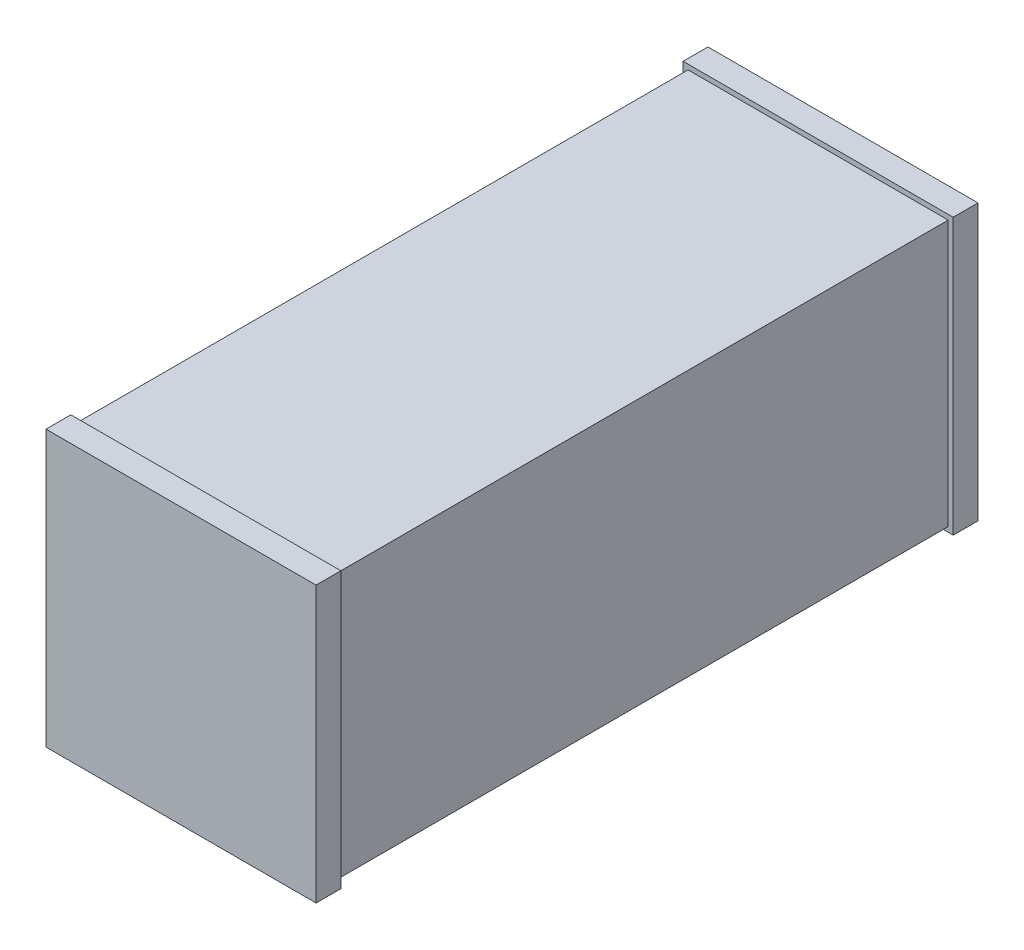
SolidWorks part; units mm, degrees
ref_plane "Front Plane" through (0, 0, 0) normal (0, 0, 1) x (1, 0, 0)
ref_plane "Top Plane" through (0, 0, 0) normal (0, 1, 0) x (1, 0, 0)
ref_plane "Right Plane" through (0, 0, 0) normal (1, 0, 0) x (0, 0, -1)
sketch "Sketch1" plane through (0, 0, 0) normal (0, 0, 1) x (1, 0, 0)
  line L1 (0, 0) -> (103.632, 0)
  line L2 (0, 0) -> (0, -105.664)
  line L3 (0, -105.664) -> (103.632, -105.664)
  line L4 (103.632, 0) -> (103.632, -105.664)
  dimension "D1" = 103.632
  dimension "D2" = 105.664
extrude "Boss-Extrude1" add sketch "Sketch1" against normal blind 9.525
sketch "Sketch2" plane through (0, 0, -9.525) normal (0, 0, -1) x (-1, 0, 0)
  line L0 (-103.632, 0) -> (0, 0) construction
  line L1 (-101.727, -1.905) -> (-1.905, -1.905)
  line L2 (-101.727, -1.905) -> (-101.727, -103.759)
  line L3 (-101.727, -103.759) -> (-1.905, -103.759)
  line L4 (-1.905, -1.905) -> (-1.905, -103.759)
  line L5 (-103.632, -105.664) -> (-103.632, 0) construction
  line L6 (0, 0) -> (0, -105.664) construction
  line L7 (0, -105.664) -> (-103.632, -105.664) construction
  dimension "D1" = 1.905
  dimension "D2" = 1.905
  dimension "D3" = 1.905
  dimension "D4" = 1.905
extrude "Boss-Extrude2" add sketch "Sketch2" along normal blind 234.95
sketch "Sketch4" plane through (0, 0, -244.475) normal (0, 0, -1) x (-1, 0, 0)
  line L8 (0, 0) -> (-103.632, 0)
  line L9 (-103.632, 0) -> (-103.632, -105.664)
  line L10 (-103.632, -105.664) -> (0, -105.664)
  line L11 (0, -105.664) -> (0, 0)
  line L12 (0, 0) -> (-103.632, 0)
  line L13 (-103.632, 0) -> (-103.632, -105.664)
  line L14 (-103.632, -105.664) -> (0, -105.664)
  line L15 (0, -105.664) -> (0, 0)
  dimension "D1" = 0
extrude "Boss-Extrude5" add sketch "Sketch4" along normal blind 9.525
sketch "Sketch5" plane through (0, -103.759, 0) normal (0, -1, 0) x (1, 0, 0)
  line L0 (101.727, -9.525) -> (1.905, -9.525) construction
  line L2 (15.621, -19.05) -> (1.905, -19.05) construction
  line L3 (1.905, -244.475) -> (1.905, -9.525) construction
  line L4 (88.011, -19.05) -> (101.727, -19.05) construction
  line L5 (101.727, -244.475) -> (101.727, -9.525) construction
  line L6 (15.621, -234.95) -> (1.905, -234.95) construction
  line L7 (88.011, -234.95) -> (101.727, -234.95) construction
  point P0 (15.621, -19.05)
  point P1 (88.011, -19.05)
  point P2 (15.621, -234.95)
  point P3 (88.011, -234.95)
  dimension "D1" = 72.39
  dimension "D2" = 215.9
  dimension "D3" = 9.525
hole_wizard "Tap Drill for #6-32 Tap1" positions "Sketch6" profile "Sketch7" hole size "#6-32" standard "ANSI Inch"
sketch "Sketch6" plane through (0, -103.759, 0) normal (0, -1, 0) x (-1, 0, 0)
  point P0 (-88.011, 234.95)
  point P3 (-15.621, 234.95)
  point P6 (-88.011, 19.05)
  point P9 (-15.621, 19.05)
sketch "Sketch7" plane through (88.011, -103.759, -234.95) normal (1, 0, 0) x (0, 0, -1)
  line L0 (0, 0) -> (0, 4.7827)
  line L1 (0, 4.7827) -> (1.3525, 3.97)
  line L2 (1.3525, 3.97) -> (1.3525, 0)
  line L5 (1.3525, 0) -> (0, 0)
  line L10 (0, 4.7827) -> (-1.3526, 3.97) construction
  line L11 (0, -6.35) -> (0, 107.95) construction
  dimension "Hole Dia." = 2.7051
  dimension "Hole Depth" = 3.97
  dimension "Drill Angle" = 118
